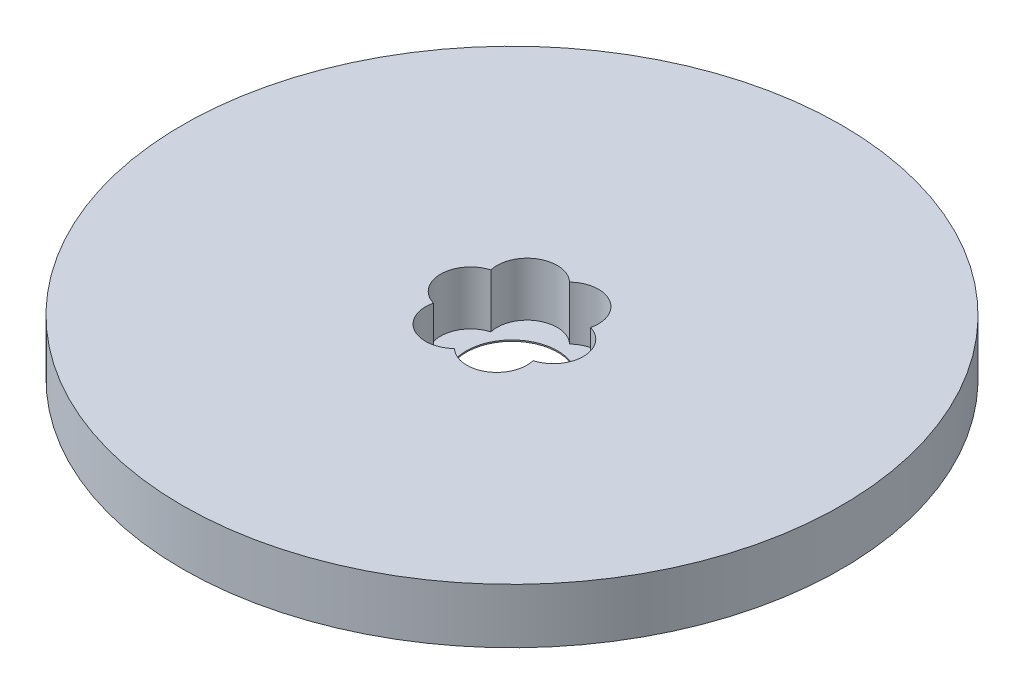
SolidWorks part; units mm, degrees
ref_plane "Front Plane" through (0, 0, 0) normal (0, 0, 1) x (1, 0, 0)
ref_plane "Top Plane" through (0, 0, 0) normal (0, 1, 0) x (1, 0, 0)
ref_plane "Right Plane" through (0, 0, 0) normal (1, 0, 0) x (0, 0, -1)
sketch "Sketch1" plane through (0, 0, 0) normal (0, 1, 0) x (1, 0, 0)
  circle A0 centre (0, 0) radius 90
  dimension "FLANGE_OD" = 180
extrude "Boss-Extrude1" add sketch "Sketch1" along normal blind 15
sketch "Sketch2" plane through (0, 0, 0) normal (0, 1, 0) x (1, 0, 0)
  circle A0 centre (0, 0) radius 12.5
  dimension "BORE_D" = 25
extrude "Cut-Extrude1" cut sketch "Sketch2" along normal through all
sketch "Sketch3" plane through (0, 15, 0) normal (0, 1, 0) x (1, 0, 0)
  circle A0 centre (0, 0) radius 11.3033 construction
  circle A1 centre (-11.3033, 0) radius 8.1908
  dimension "BOLT_D" = 16.3816
  dimension "BOLT_PCD" = 22.6067
extrude "Cut-Extrude2" cut sketch "Sketch3" against normal blind 14.6615
pattern_circular "CirPattern1" count 6 over 360 about axis through (0, 0, 0) along (0, 1, 0) of "Cut-Extrude2"
